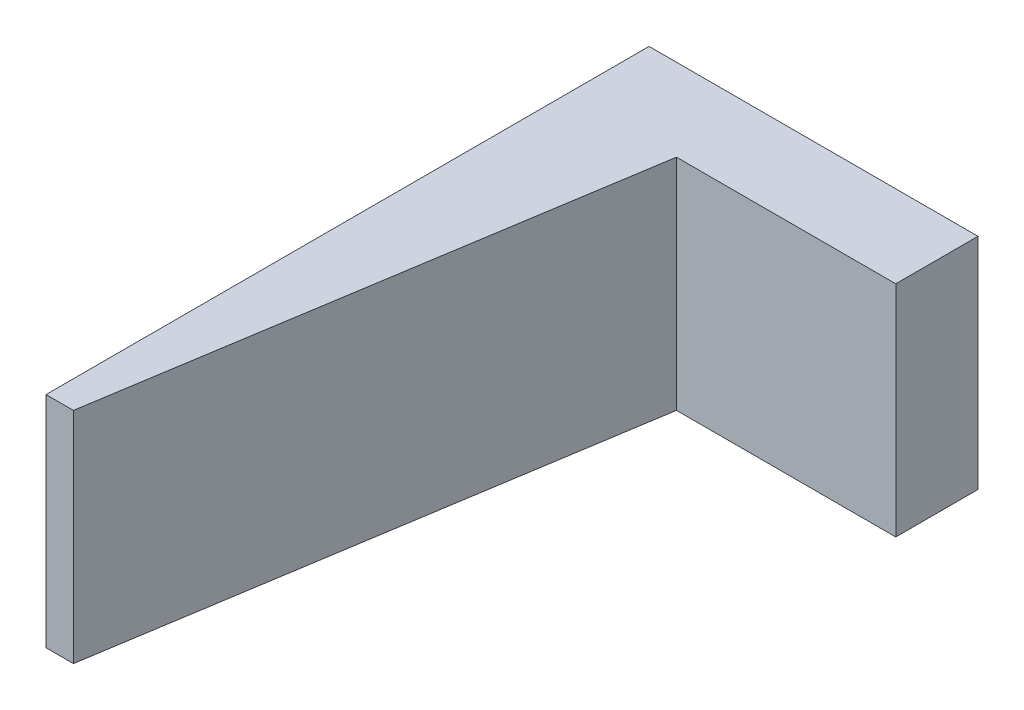
SolidWorks part; units mm, degrees
ref_plane "Front" through (0, 0, 0) normal (0, 0, 1) x (1, 0, 0)
ref_plane "Top" through (0, 0, 0) normal (0, 1, 0) x (1, 0, 0)
ref_plane "Right" through (0, 0, 0) normal (1, 0, 0) x (0, 0, -1)
sketch "Sketch1" plane through (0, 0, 0) normal (0, 1, 0) x (1, 0, 0)
  line L0 (0, 0) -> (38.1, 0)
  line L1 (38.1, 0) -> (38.1, -9.525)
  line L2 (38.1, -9.525) -> (12.7, -9.525)
  line L3 (12.7, -9.525) -> (3.175, -69.85)
  line L4 (3.175, -69.85) -> (0, -69.85)
  line L5 (0, -69.85) -> (0, 0)
  dimension "D1" = 38.1
  dimension "D2" = 9.525
  dimension "D3" = 3.175
  dimension "D4" = 25.4
  dimension "D5" = 69.85
extrude "Boss-Extrude1" add sketch "Sketch1" along normal blind 25.4
